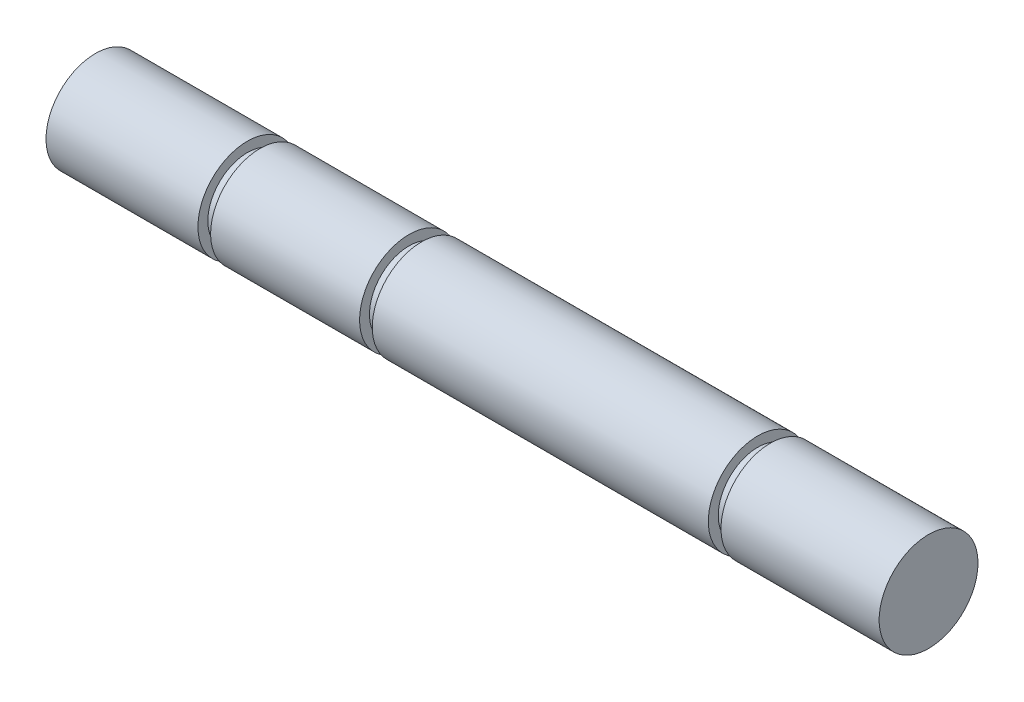
SolidWorks part; units mm, degrees
material "Plain Carbon Steel"
ref_plane "Front Plane" through (0, 0, 0) normal (0, 0, 1) x (1, 0, 0)
ref_plane "Top Plane" through (0, 0, 0) normal (0, 1, 0) x (1, 0, 0)
ref_plane "Right Plane" through (0, 0, 0) normal (1, 0, 0) x (0, 0, -1)
sketch "Sketch1" plane through (0, 0, 0) normal (1, 0, 0) x (0, 0, -1)
  circle A0 centre (0, 0) radius 2.5
  dimension "D1" = 5
extrude "Boss-Extrude1" add sketch "Sketch1" along normal blind 100
ref_plane "Plane1" through (92, 0, 0) normal (1, 0, 0) x (0, 0, -1)
sketch "Sketch2" plane through (92, 0, 0) normal (1, 0, 0) x (0, 0, -1)
  circle A0 centre (0, 0) radius 2
  circle A1 centre (0, 0) radius 2.5
  dimension "D1" = 4
  dimension "D2" = 5
extrude "Cut-Extrude1" cut sketch "Sketch2" against normal blind 0.64
ref_plane "Plane2" through (74.36, 0, 0) normal (1, 0, 0) x (0, 0, -1)
sketch "Sketch3" plane through (74.36, 0, 0) normal (1, 0, 0) x (0, 0, -1)
  circle A0 centre (0, 0) radius 2.5
  circle A1 centre (0, 0) radius 2
  dimension "D1" = 4
  dimension "D2" = 5
extrude "Cut-Extrude2" cut sketch "Sketch3" against normal blind 0.64
ref_plane "Plane3" through (57.86, 0, 0) normal (-1, 0, 0) x (0, 0, 1)
sketch "Sketch4" plane through (57.86, 0, 0) normal (-1, 0, 0) x (0, 0, 1)
  circle A0 centre (0, 0) radius 2.5
  dimension "D1" = 5
extrude "Cut-Extrude3" cut sketch "Sketch4" along normal up to surface (57.86 mm away) up to face at (0, 0, -2.5)
ref_plane "Plane4" through (66.185, 0, 0) normal (-1, 0, 0) x (0, 0, 1)
sketch "Sketch6" plane through (66.185, 0, 0) normal (-1, 0, 0) x (0, 0, 1)
  circle A0 centre (0, 0) radius 2
  circle A1 centre (0, 0) radius 2.5
  dimension "D1" = 5
  dimension "D2" = 4
extrude "Cut-Extrude4" cut sketch "Sketch6" along normal blind 0.64
